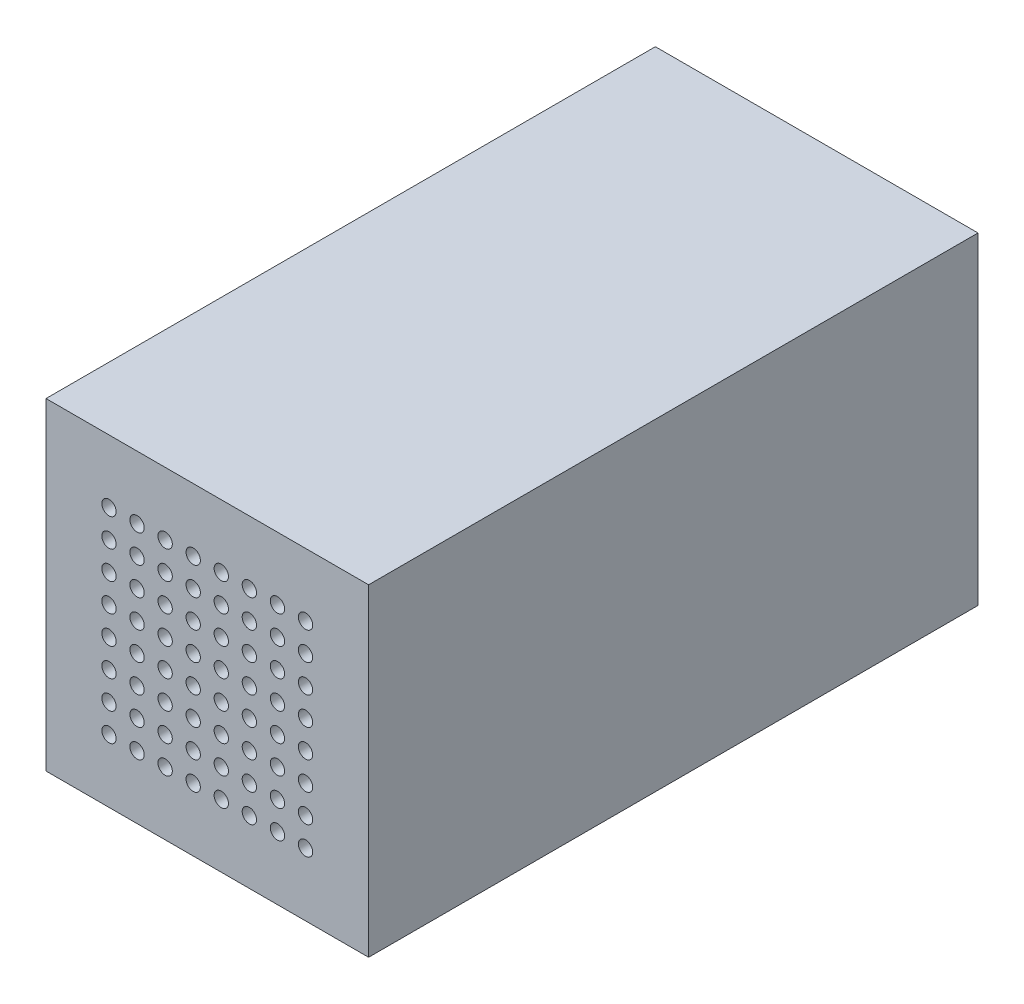
SolidWorks part; units mm, degrees
ref_plane "Front Plane" through (0, 0, 0) normal (0, 0, 1) x (1, 0, 0)
ref_plane "Top Plane" through (0, 0, 0) normal (0, 1, 0) x (1, 0, 0)
ref_plane "Right Plane" through (0, 0, 0) normal (1, 0, 0) x (0, 0, -1)
ref_plane "Plane1" through (0, 0, 43) normal (0, 0, 1) x (1, 0, 0)
sketch "Sketch2" plane through (0, 0, 43) normal (0, 0, 1) x (1, 0, 0)
  line L1 (-10, 10) -> (10, 10)
  line L2 (-10, 10) -> (-10, -10)
  line L3 (-10, -10) -> (10, -10)
  line L4 (10, 10) -> (10, -10)
  line L5 (-13.5, 13.5) -> (13.5, 13.5)
  line L6 (-13.5, 13.5) -> (-13.5, -13.5)
  line L7 (-13.5, -13.5) -> (13.5, -13.5)
  line L8 (13.5, 13.5) -> (13.5, -13.5)
  dimension "D1" = 20
  dimension "D2" = 20
  dimension "D3" = 27
  dimension "D4" = 27
  dimension "D5" = 10
  dimension "D6" = 10
  dimension "D7" = 13.5
  dimension "D8" = 13.5
sketch "Sketch5" plane through (0, 0, 43) normal (0, 0, 1) x (1, 0, 0)
  line L4 (-10, 10) -> (10, 10) construction
  line L5 (-10, 10) -> (-10, -10) construction
  line L6 (-10, -10) -> (10, -10) construction
  line L7 (10, 10) -> (10, -10) construction
  circle A0 centre (-8.23, 8.23) radius 0.6
  circle A1 centre (-5.88, 8.23) radius 0.6
  circle A2 centre (-3.53, 8.23) radius 0.6
  circle A3 centre (-1.18, 8.23) radius 0.6
  circle A4 centre (1.17, 8.23) radius 0.6
  circle A5 centre (3.52, 8.23) radius 0.6
  circle A6 centre (5.87, 8.23) radius 0.6
  circle A7 centre (8.22, 8.23) radius 0.6
  circle A8 centre (-5.88, 5.88) radius 0.6
  circle A9 centre (-3.53, 5.88) radius 0.6
  circle A10 centre (-1.18, 5.88) radius 0.6
  circle A11 centre (1.17, 5.88) radius 0.6
  circle A12 centre (3.52, 5.88) radius 0.6
  circle A13 centre (5.87, 5.88) radius 0.6
  circle A14 centre (8.22, 5.88) radius 0.6
  circle A15 centre (-5.88, 3.53) radius 0.6
  circle A16 centre (-3.53, 3.53) radius 0.6
  circle A17 centre (-1.18, 3.53) radius 0.6
  circle A18 centre (1.17, 3.53) radius 0.6
  circle A19 centre (3.52, 3.53) radius 0.6
  circle A20 centre (5.87, 3.53) radius 0.6
  circle A21 centre (8.22, 3.53) radius 0.6
  circle A22 centre (-5.88, 1.18) radius 0.6
  circle A23 centre (-3.53, 1.18) radius 0.6
  circle A24 centre (-1.18, 1.18) radius 0.6
  circle A25 centre (1.17, 1.18) radius 0.6
  circle A26 centre (3.52, 1.18) radius 0.6
  circle A27 centre (5.87, 1.18) radius 0.6
  circle A28 centre (8.22, 1.18) radius 0.6
  circle A29 centre (-5.88, -1.17) radius 0.6
  circle A30 centre (-3.53, -1.17) radius 0.6
  circle A31 centre (-1.18, -1.17) radius 0.6
  circle A32 centre (1.17, -1.17) radius 0.6
  circle A33 centre (3.52, -1.17) radius 0.6
  circle A34 centre (5.87, -1.17) radius 0.6
  circle A35 centre (8.22, -1.17) radius 0.6
  circle A36 centre (-5.88, -3.52) radius 0.6
  circle A37 centre (-3.53, -3.52) radius 0.6
  circle A38 centre (-1.18, -3.52) radius 0.6
  circle A39 centre (1.17, -3.52) radius 0.6
  circle A40 centre (3.52, -3.52) radius 0.6
  circle A41 centre (5.87, -3.52) radius 0.6
  circle A42 centre (8.22, -3.52) radius 0.6
  circle A43 centre (-5.88, -5.87) radius 0.6
  circle A44 centre (-3.53, -5.87) radius 0.6
  circle A45 centre (-1.18, -5.87) radius 0.6
  circle A46 centre (1.17, -5.87) radius 0.6
  circle A47 centre (3.52, -5.87) radius 0.6
  circle A48 centre (5.87, -5.87) radius 0.6
  circle A49 centre (8.22, -5.87) radius 0.6
  circle A50 centre (-5.88, -8.22) radius 0.6
  circle A51 centre (-3.53, -8.22) radius 0.6
  circle A52 centre (-1.18, -8.22) radius 0.6
  circle A53 centre (1.17, -8.22) radius 0.6
  circle A54 centre (3.52, -8.22) radius 0.6
  circle A55 centre (5.87, -8.22) radius 0.6
  circle A56 centre (8.22, -8.22) radius 0.6
  circle A57 centre (-8.23, 5.88) radius 0.6
  circle A58 centre (-8.23, 3.53) radius 0.6
  circle A59 centre (-8.23, 1.18) radius 0.6
  circle A60 centre (-8.23, -1.17) radius 0.6
  circle A61 centre (-8.23, -3.52) radius 0.6
  circle A62 centre (-8.23, -5.87) radius 0.6
  circle A63 centre (-8.23, -8.22) radius 0.6
  dimension "D1" = 8
  dimension "D3" = 1.2
  dimension "D4" = 2.35
  dimension "D5" = 1.77
  dimension "D6" = 1.77
  dimension "D8" = 2.35
  dimension "D2" = 8
extrude "Boss-Extrude1" add sketch "Sketch2" along normal blind 8 contours L6 L7 L8 L5
extrude "Cut-Extrude2" cut sketch "Sketch5" along normal blind 8
extrude "Boss-Extrude2" add sketch "Sketch2<6>" against normal blind 43
sketch "Sketch2<6>" plane through (0, 0, 43) normal (0, 0, 1) x (1, 0, 0) same geometry as "Sketch2"
